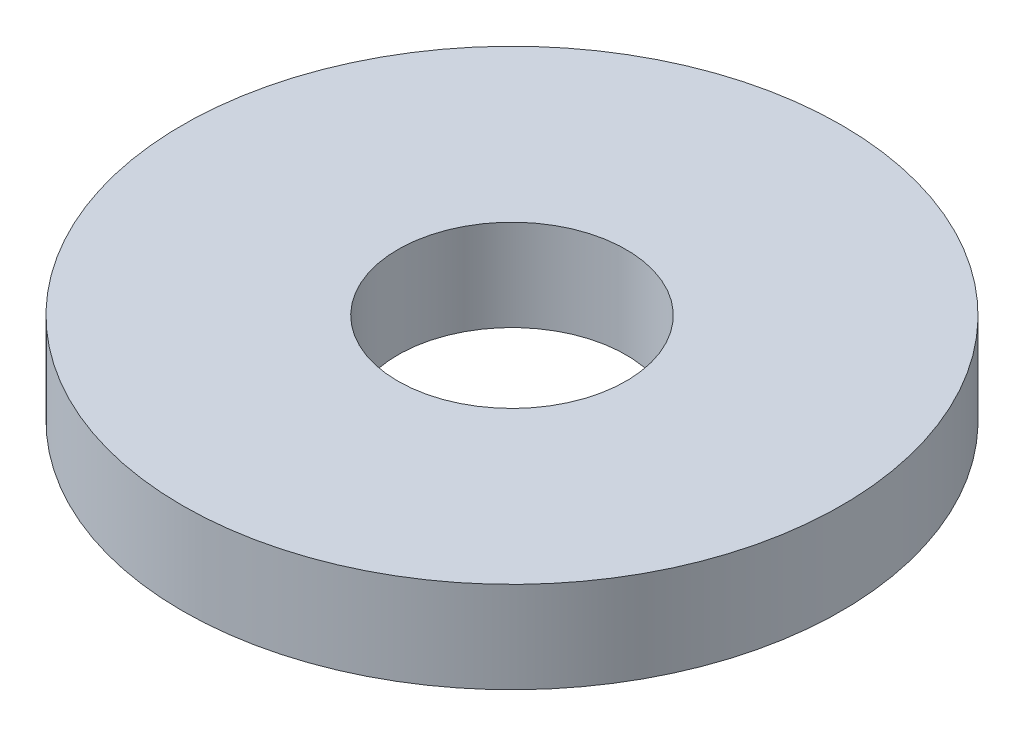
SolidWorks part; units mm, degrees
ref_plane "Front Plane" through (0, 0, 0) normal (0, 0, 1) x (1, 0, 0)
ref_plane "Top Plane" through (0, 0, 0) normal (0, 1, 0) x (1, 0, 0)
ref_plane "Right Plane" through (0, 0, 0) normal (1, 0, 0) x (0, 0, -1)
sketch "Sketch1" plane through (0, 0, 0) normal (0, 1, 0) x (1, 0, 0)
  circle A0 centre (0, 0) radius 65
  dimension "FLANGE_OD" = 130
extrude "Boss-Extrude1" add sketch "Sketch1" along normal blind 18
sketch "Sketch2" plane through (0, 0, 0) normal (0, 1, 0) x (1, 0, 0)
  circle A0 centre (0, 0) radius 22.5
  dimension "BORE_D" = 45
extrude "Cut-Extrude1" cut sketch "Sketch2" along normal through all
sketch "Sketch3" plane through (0, 18, 0) normal (0, 1, 0) x (1, 0, 0)
  circle A0 centre (0, 0) radius 15.1481 construction
  circle A1 centre (-15.1481, 0) radius 2.1485
  dimension "BOLT_D" = 4.297
  dimension "BOLT_PCD" = 30.2963
extrude "Cut-Extrude2" cut sketch "Sketch3" against normal blind 14.2296 rebuild error yes
pattern_circular "CirPattern1" count 4 over 360 rebuild error yes
